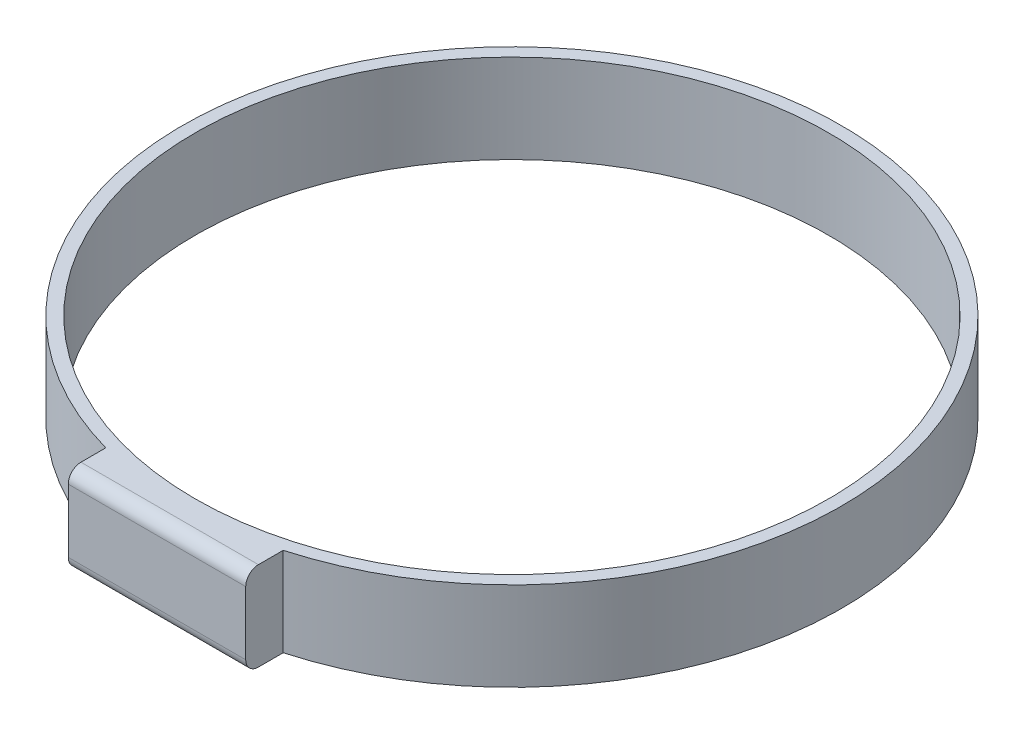
SolidWorks part; units mm, degrees
material "AISI 316 Stainless Steel Sheet (SS)"
ref_plane "Front Plane" through (0, 0, 0) normal (0, 0, 1) x (1, 0, 0)
ref_plane "Top Plane" through (0, 0, 0) normal (0, 1, 0) x (1, 0, 0)
ref_plane "Right Plane" through (0, 0, 0) normal (1, 0, 0) x (0, 0, -1)
sketch "Sketch1" plane through (0, 0, 0) normal (0, 1, 0) x (1, 0, 0)
  circle A0 centre (0, 0) radius 25
  circle A1 centre (0, 0) radius 26
  dimension "D1" = 50
  dimension "D2" = 1
extrude "Boss-Extrude1" add sketch "Sketch1" along normal blind 7
ref_plane "Plane1" through (0, 0, 25) normal (0, 0, 1) x (1, 0, 0)
sketch "Sketch2" plane through (0, 0, 25) normal (0, 0, 1) x (1, 0, 0)
  line L0 (25, 7) -> (-25, 7) construction
  line L1 (-7, 7) -> (7, 7)
  line L2 (-7, 7) -> (-7, 0)
  line L3 (-7, 0) -> (7, 0)
  line L4 (7, 7) -> (7, 0)
  line L5 (-26, 0) -> (26, 0) construction
  dimension "D1" = 14
extrude "Boss-Extrude2" add sketch "Sketch2" along normal blind 3
fillet "Fillet1" radius 1 2 edges at (0, 0, 28) (0, 7, 28)
